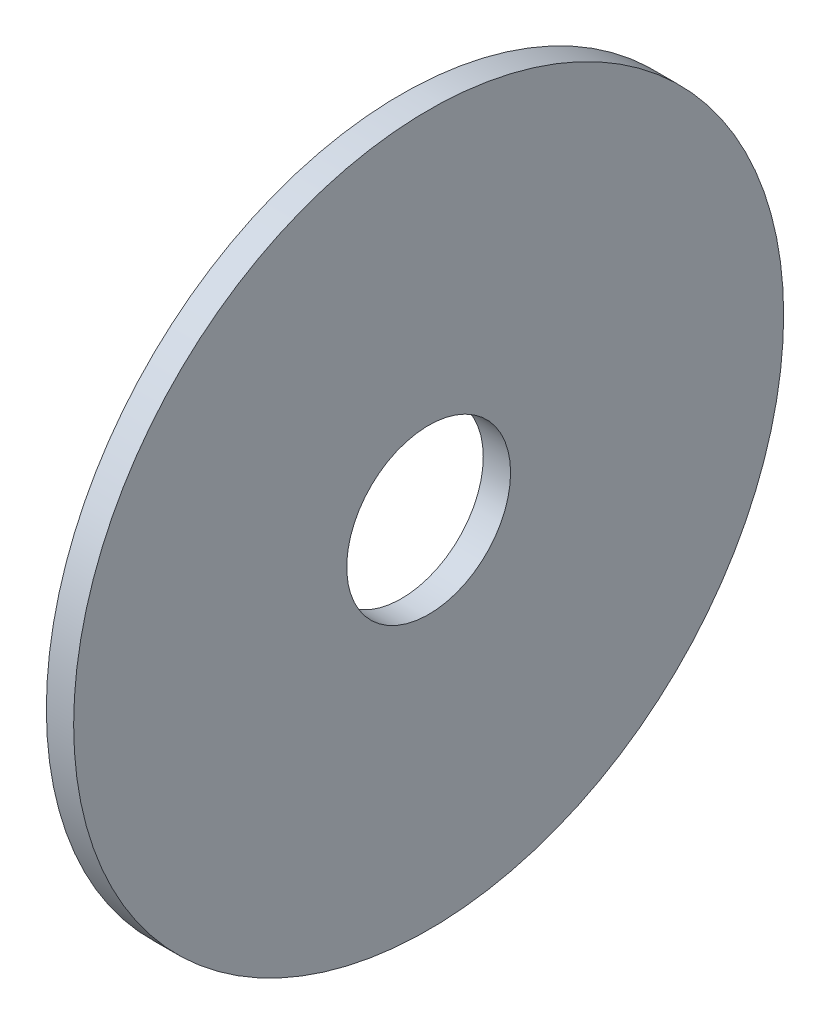
SolidWorks part; units mm, degrees
material "AISI 304"
ref_plane "Спереди" through (0, 0, 0) normal (0, 0, 1) x (1, 0, 0)
ref_plane "Сверху" through (0, 0, 0) normal (0, 1, 0) x (1, 0, 0)
ref_plane "Справа" through (0, 0, 0) normal (1, 0, 0) x (0, 0, -1)
sketch "Эскиз1" plane through (0, 0, 0) normal (1, 0, 0) x (0, 0, -1)
  circle A0 centre (0, 0) radius 39
  circle A1 centre (0, 0) radius 9
  dimension "D1" = 18
  dimension "D2" = 78
base flange "Базовая кромка1" sketch "Эскиз1" thickness 3 reverse thickness direction no parameters "D1"=4
sketch "Сгиб-Линии1" plane through (0, 0, 0) normal (0, 1, 0) x (1, 0, 0)
sketch "Граничная рамка1" plane through (0, 0, 0) normal (0, 1, 0) x (1, 0, 0)
sheet metal parameters "Листовой металл3" thickness 3 parameters "D1"=4
flat pattern "Развертка3" [suppressed]
sketch "Сгиб-Линии2" plane through (0, 0, 0) normal (0, 1, 0) x (1, 0, 0)
sketch "Граничная рамка2" [suppressed] plane through (0, 0, 0) normal (0, 1, 0) x (1, 0, 0)
